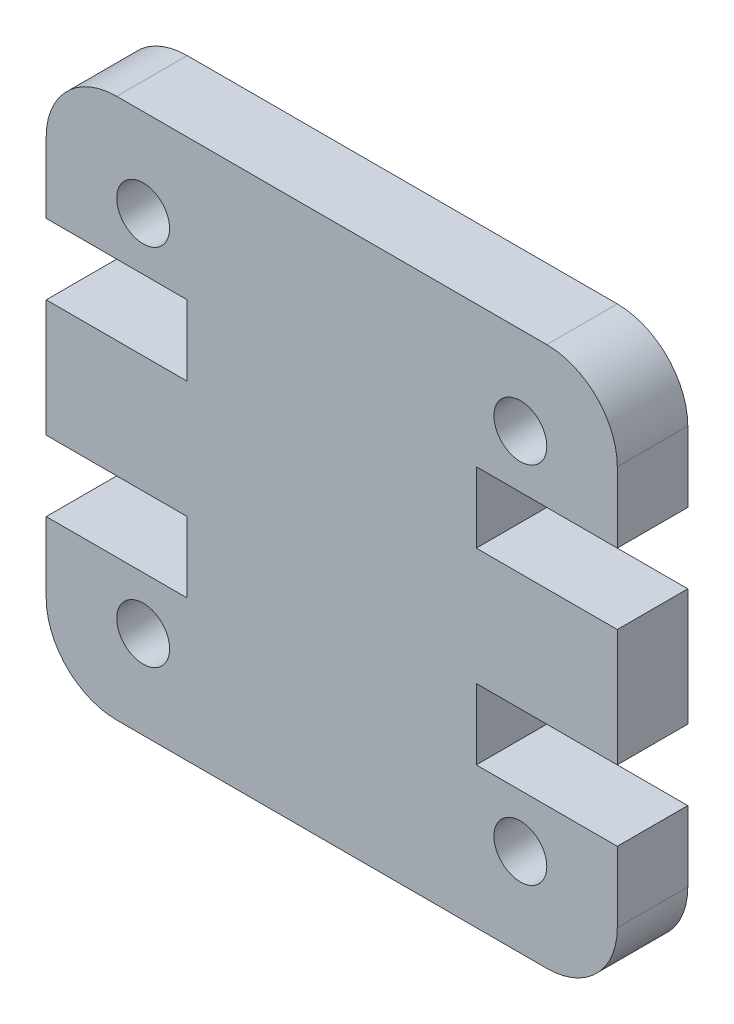
SolidWorks part; units mm, degrees
ref_plane "Front Plane" through (0, 0, 0) normal (0, 0, 1) x (1, 0, 0)
ref_plane "Top Plane" through (0, 0, 0) normal (0, 1, 0) x (1, 0, 0)
ref_plane "Right Plane" through (0, 0, 0) normal (1, 0, 0) x (0, 0, -1)
sketch "Sketch1" plane through (0, 0, 0) normal (0, 0, 1) x (1, 0, 0)
  line L12 (0, 9.325) -> (0, 6)
  line L13 (0, 11.325) -> (4, 11.325)
  line L14 (4, 11.325) -> (4, 9.325)
  line L15 (4, 9.325) -> (0, 9.325)
  line L16 (0, 11.325) -> (0, 13.325)
  line L17 (16.2, 9.325) -> (16.2, 6)
  line L18 (2, 15.325) -> (14.2, 15.325)
  line L19 (2, 0) -> (14.2, 0)
  line L20 (16.2, 4) -> (16.2, 2)
  line L21 (4, 4) -> (0, 4)
  line L22 (0, 6) -> (4, 6)
  line L23 (4, 6) -> (4, 4)
  line L24 (0, 4) -> (0, 2)
  line L25 (16.2, 11.325) -> (16.2, 13.325)
  line L26 (12.2, 9.325) -> (16.2, 9.325)
  line L27 (12.2, 6) -> (12.2, 4)
  line L28 (12.2, 11.325) -> (12.2, 9.325)
  line L29 (16.2, 11.325) -> (12.2, 11.325)
  line L30 (12.2, 4) -> (16.2, 4)
  line L31 (16.2, 6) -> (12.2, 6)
  arc A8 (2, 15.325) -> (0, 13.325) centre (2, 13.325) ccw
  arc A9 (16.2, 13.325) -> (14.2, 15.325) centre (14.2, 13.325) ccw
  arc A10 (14.2, 0) -> (16.2, 2) centre (14.2, 2) ccw
  arc A11 (0, 2) -> (2, 0) centre (2, 2) ccw
  circle A12 centre (13.45, 2.5) radius 0.75
  circle A13 centre (2.75, 2.5) radius 0.75
  circle A14 centre (13.45, 12.825) radius 0.75
  circle A15 centre (2.75, 12.825) radius 0.75
extrude "Boss-Extrude1" add sketch "Sketch1" along normal blind 2
